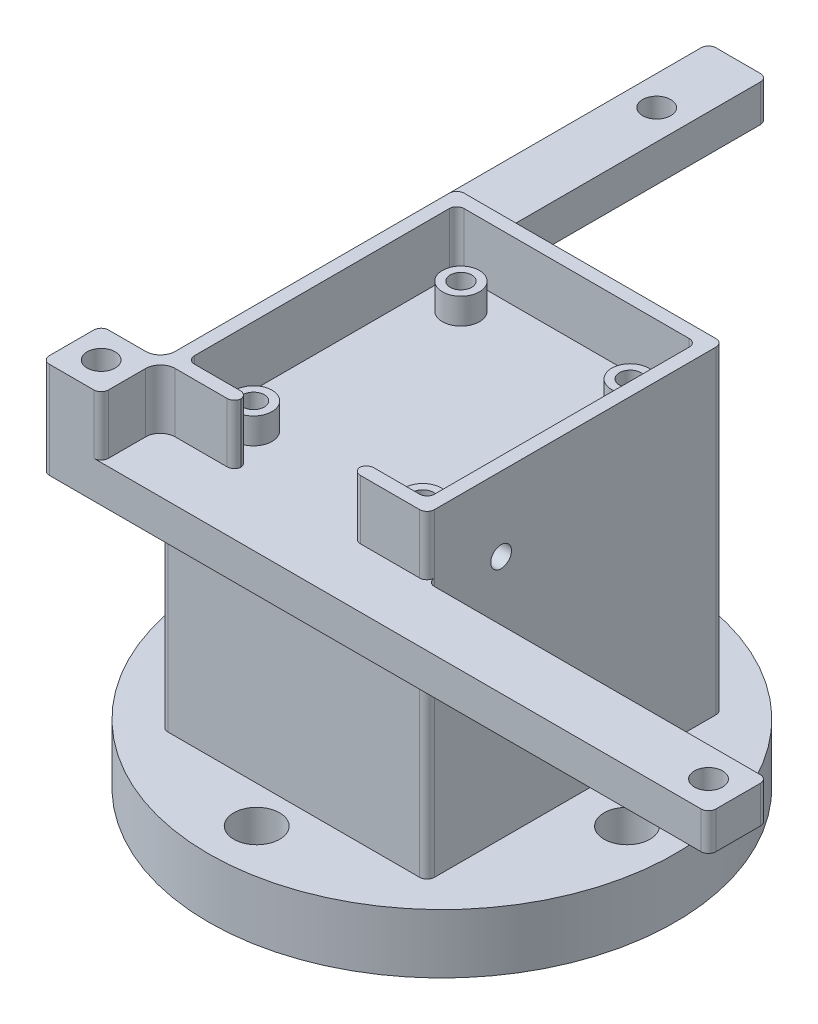
SolidWorks part; units mm, degrees
ref_plane "Front Plane" through (0, 0, 0) normal (0, 0, 1) x (1, 0, 0)
ref_plane "Top Plane" through (0, 0, 0) normal (0, 1, 0) x (1, 0, 0)
ref_plane "Right Plane" through (0, 0, 0) normal (1, 0, 0) x (0, 0, -1)
sketch "Sketch1" plane through (0, 0, 0) normal (0, 1, 0) x (1, 0, 0)
  line L1 (-18, 20) -> (18, 20)
  line L2 (-18, 20) -> (-18, -20)
  line L3 (-18, -20) -> (18, -20)
  line L4 (18, 20) -> (18, -20)
  line L5 (-18, 20) -> (18, -20) construction
  line L6 (-18, -20) -> (18, 20) construction
  point P0 (0, 0)
  dimension "D1" = 36
  dimension "D2" = 40
extrude "Boss-Extrude1" add sketch "Sketch1" along normal blind 5
sketch "Sketch2" plane through (0, 5, 0) normal (0, 1, 0) x (1, 0, 0)
  line L2 (-18, -20) -> (-18, 62)
  line L3 (-18, 62) -> (-26, 62)
  line L4 (-26, -28) -> (-26, 62)
  line L5 (-18, -20) -> (64, -20)
  line L7 (-26, -28) -> (64, -28)
  line L8 (64, -20) -> (64, -28)
  point P3 (-26, -12)
  point P8 (-32.7128, -31.0991)
  point P9 (64, -12)
  point P10 (-26, -29.4163)
  dimension "D1" = 90
  dimension "D2" = 8
extrude "Boss-Extrude2" add sketch "Sketch2" against normal up to surface (5 mm away) up to face at (0, 0, 0)
sketch "Sketch3" plane through (0, 5, 0) normal (0, 1, 0) x (1, 0, 0)
  line L0 (18, 20) -> (-18, 20) construction
  line L1 (-18, 20) -> (18, 20)
  line L2 (-18, 20) -> (-18, -18)
  line L3 (-16, -20) -> (-8, -20)
  line L4 (18, 20) -> (18, -20)
  line L5 (-16.2, 18.2) -> (16.2, 18.2)
  line L6 (-16.2, 18.2) -> (-16.2, -18.2)
  line L7 (-16.2, -18.2) -> (-8, -18.2)
  line L8 (16.2, 18.2) -> (16.2, -18.2)
  line L9 (0, 18.2) -> (0, 20) construction
  line L10 (-16.2, 18.2) -> (-18, 18.2) construction
  line L11 (-8, -18.2) -> (-8, -20)
  line L12 (-26, -28) -> (-18, -28)
  line L13 (-26, -28) -> (-26, -20)
  line L14 (-26, -20) -> (-20, -20)
  line L15 (-18, -28) -> (-18, -22)
  line L16 (8, -18.2) -> (8, -20)
  line L17 (0, 0) -> (0, 18.2) construction
  line L18 (8, -18.2) -> (16.2, -18.2)
  line L19 (8, -20) -> (18, -20)
  arc A0 (-20, -20) -> (-18, -18) centre (-20, -18) ccw
  arc A1 (-16, -20) -> (-18, -22) centre (-16, -22) ccw
  point P25 (-18, -20)
  dimension "D2" = 2
  dimension "D1" = 1.8
  dimension "D3" = 16
extrude "Boss-Extrude4" add sketch "Sketch3" along normal blind 8
fillet "Fillet1" radius 1 11 edges at (-26, 6.5, 28) (-26, 9, 20) (-18, 9, 28) (8, 9, 20) (8, 9, 18.2) (16.2, 9, 18.2) (16.2, 9, -18.2) (-16.2, 9, -18.2) (-16.2, 9, 18.2) (-8, 9, 18.2) (-8, 9, 20)
fillet "Fillet2" radius 1 2 edges at (-18, 9, -20) (18, 9, 20)
fillet "Fillet3" radius 1 4 edges at (-26, 2.5, -62) (-18, 2.5, -62) (64, 2.5, 20) (64, 2.5, 28)
sketch "Sketch4" plane through (0, 13, 0) normal (0, 1, 0) x (1, 0, 0)
  line L0 (-26, -24) -> (-22, -24) construction
  line L1 (-26, -21) -> (-26, -27) construction
  line L2 (-22, -24) -> (60, -24) construction
  line L3 (-22, -28) -> (-22, -24) construction
  line L4 (-25, -28) -> (-19, -28) construction
  line L5 (-22, -24) -> (-22, 51) construction
  circle A0 centre (-22, -24) radius 1.9
  circle A1 centre (-22, 51) radius 1.9
  circle A2 centre (60, -24) radius 1.9
  dimension "D1" = 3.8
  dimension "D2" = 82
  dimension "D3" = 75
extrude "Cut-Extrude1" cut sketch "Sketch4" against normal through all
sketch "Sketch5" plane through (0, 5, 0) normal (0, 1, 0) x (1, 0, 0)
  line L0 (0, 0) -> (0, 14) construction
  line L1 (-11.425, 14) -> (11.425, 14) construction
  line L2 (-11.425, 14) -> (-11.425, -14) construction
  line L3 (-11.425, -14) -> (11.425, -14) construction
  line L4 (11.425, 14) -> (11.425, -14) construction
  line L5 (0, 18.2) -> (0, 14) construction
  line L6 (-15.2, 18.2) -> (15.2, 18.2) construction
  line L7 (-16.2, 0) -> (-11.425, 0) construction
  line L8 (-16.2, -17.2) -> (-16.2, 17.2) construction
  circle A0 centre (-11.425, 14) radius 2.5
  circle A1 centre (11.425, 14) radius 2.5
  circle A2 centre (11.425, -14) radius 2.5
  circle A3 centre (-11.425, -14) radius 2.5
  dimension "D1" = 5
  dimension "D2" = 22.85
  dimension "D3" = 28
extrude "Boss-Extrude5" add sketch "Sketch5" along normal blind 3.5
sketch "Sketch6" plane through (0, 8.5, 0) normal (0, 1, 0) x (1, 0, 0)
  circle A0 centre (-11.425, 14) radius 1.45
  circle A1 centre (11.425, 14) radius 1.45
  circle A2 centre (11.425, -14) radius 1.45
  circle A3 centre (-11.425, -14) radius 1.45
  dimension "D1" = 2.9
extrude "Cut-Extrude2" cut sketch "Sketch6" against normal blind 7
sketch "Sketch7" plane through (0, 0, 0) normal (0, -1, 0) x (1, 0, 0)
  line L0 (18, 20) -> (63, 20) construction
  line L1 (18, -20) -> (-18, -20)
  line L2 (18, -20) -> (18, 20)
  line L3 (18, 20) -> (-18, 20)
  line L4 (-18, -20) -> (-18, 20)
  line L5 (18, -20) -> (-18, 20) construction
  line L6 (18, 20) -> (-18, -20) construction
  line L7 (-18, -61) -> (-18, -20) construction
  point P0 (0, 0)
extrude "Boss-Extrude6" add sketch "Sketch7" along normal blind 30
sketch "Sketch8" plane through (0, -30, 0) normal (0, -1, 0) x (1, 0, 0)
  circle A0 centre (0, 0) radius 31.5
  dimension "D1" = 63
extrude "Boss-Extrude7" add sketch "Sketch8" along normal blind 8
sketch "Sketch9" plane through (0, -38, 0) normal (0, -1, 0) x (1, 0, 0)
  circle A0 centre (0, 0) radius 25 construction
  circle A1 centre (0, 25) radius 3.1
  circle A2 centre (-25, 0) radius 3.1
  circle A3 centre (25, 0) radius 3.1
  circle A4 centre (0, -25) radius 3.1
  dimension "D1" = 50
  dimension "D2" = 6.2
extrude "Cut-Extrude3" cut sketch "Sketch9" against normal up to surface (8 mm away) up to face at (0, -30, -31.5)
fillet "Fillet5" radius 1 4 edges at (-18, -15, 20) (18, -15, 20) (18, -8.5, -20) (-18, -15, -20)
fillet "Fillet6" radius 1 2 edges at (-18, 2.5, -20) (18, 2.5, 20)
sketch "Sketch10" plane through (18, 0, 0) normal (1, 0, 0) x (0, 0, -1)
  line L0 (-10, 13) -> (-10, -12) construction
  line L3 (-19, 13) -> (19, 13) construction
  line L4 (0, 0) -> (-10, 0) construction
  circle A0 centre (-10, -12) radius 1.4
  circle A1 centre (-10, 3) radius 1.4
  point P2 (0, 0)
  dimension "D1" = 2.8
  dimension "D2" = 15
  dimension "D3" = 25
  dimension "D4" = 10
extrude "Cut-Extrude4" cut sketch "Sketch10" against normal blind 10
